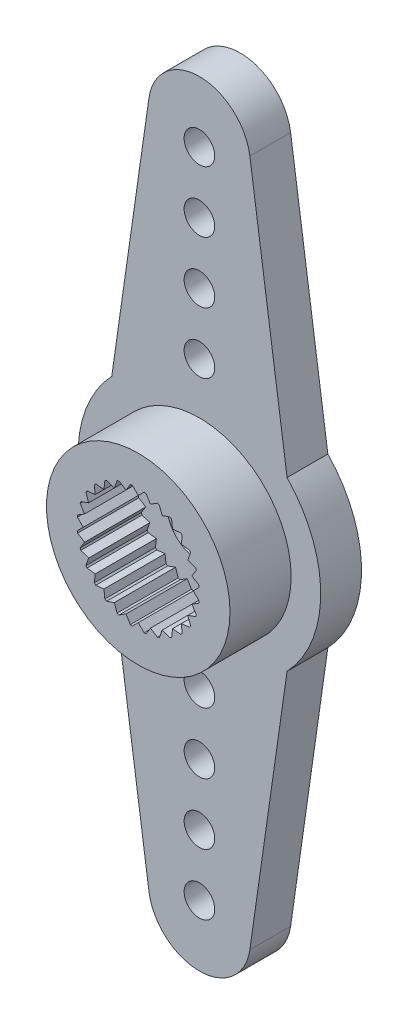
SolidWorks part; units mm, degrees
ref_plane "Plan de face" through (0, 0, 0) normal (0, 0, 1) x (1, 0, 0)
ref_plane "Plan de dessus" through (0, 0, 0) normal (0, 1, 0) x (1, 0, 0)
ref_plane "Plan de droite" through (0, 0, 0) normal (1, 0, 0) x (0, 0, -1)
sketch "Esquisse1" plane through (0, 0, 0) normal (0, 0, 1) x (1, 0, 0)
  circle A0 centre (0, 0) radius 5.95
  circle A1 centre (0, 0) radius 1.6
  dimension "D1" = 11.9
  dimension "D2" = 3.2
extrude "Boss.-Extru.1" add sketch "Esquisse1" along normal blind 5
sketch "Esquisse2" plane through (0, 0, 5) normal (0, 0, 1) x (1, 0, 0)
  circle A0 centre (0, 0) radius 3
  dimension "D1" = 6
extrude "Enlèv. mat.-Extru.1" cut sketch "Esquisse2" against normal blind 3
sketch "Esquisse3" plane through (0, 0, 5) normal (0, 0, 1) x (1, 0, 0)
  circle A0 centre (0, 0) radius 5.95
  circle A1 centre (0, 0) radius 4.5
  circle A2 centre (0, 0) radius 3 construction
  circle A3 centre (0, 0) radius 5.95 construction
  dimension "D1" = 1.5
extrude "Enlèv. mat.-Extru.2" cut sketch "Esquisse3" against normal blind 3
sketch "Esquisse4" plane through (0, 0, 0) normal (0, 0, -1) x (-1, 0, 0)
  line L0 (-4.3, 4.1125) -> (-2.4747, 16.8545)
  line L1 (2.4747, 16.8545) -> (4.3, 4.1125)
  line L2 (-5.2729, 19) -> (6.8365, 19) construction
  line L3 (0, 0) -> (0, 24.2526) construction
  circle A0 centre (0, 0) radius 5.95 construction
  arc A1 (-2.4747, 16.8545) -> (2.4747, 16.8545) centre (0, 16.5) cw
  arc A2 (-4.3, 4.1125) -> (4.3, 4.1125) centre (0, 0) cw
  dimension "D2" = 2.5
  dimension "D1" = 8.6
  dimension "D3" = 19
extrude "Boss.-Extru.2" add sketch "Esquisse4" against normal up to surface (2 mm away) up to face at (4.5, 0, 2)
pattern_circular "Répétition circulaire1" count 2 every 180 about axis through (0, 0, 5) along (0, 0, -1) of "Boss.-Extru.2"
sketch "Esquisse5" plane through (0, 0, 0) normal (0, 0, -1) x (-1, 0, 0)
  line L0 (0, 0) -> (0, 20.4605) construction
  circle A0 centre (0, 7) radius 0.75
  circle A1 centre (0, 10) radius 0.75
  circle A2 centre (0, 13) radius 0.75
  circle A3 centre (0, 16) radius 0.75
  dimension "D5" = 1.5
  dimension "D6" = 1.5
  dimension "D7" = 1.5
  dimension "D8" = 1.5
  dimension "D1" = 7
  dimension "D2" = 3
  dimension "D3" = 3
  dimension "D4" = 3
extrude "Enlèv. mat.-Extru.3" cut sketch "Esquisse5" against normal blind 3
pattern_circular "Répétition circulaire2" count 2 every 180 about axis through (0, 0, 5) along (0, 0, -1) of "Enlèv. mat.-Extru.3" reverse direction yes
sketch "Esquisse6" plane through (0, 0, 5) normal (0, 0, 1) x (1, 0, 0)
  line L0 (-1.598, 3) -> (1.8482, 3) construction
  line L1 (0, 0) -> (0, 5.9454) construction
  line L2 (-0.3, 3) -> (0, 2.7)
  line L3 (0, 2.7) -> (0.3, 3)
  line L4 (0.3, 3) -> (-0.3, 3)
  circle A0 centre (0, 0) radius 3 construction
  dimension "D1" = 0.3
  dimension "D2" = 0.6
extrude "Boss.-Extru.3" add sketch "Esquisse6" against normal up to surface (3 mm away) up to face at (1.6, 0, 2)
pattern_circular "Répétition circulaire3" count 28 over 360 about axis through (0, 0, 2) along (0, 0, 1) of "Boss.-Extru.3"
sketch "Esquisse7" plane through (0, 0, 0) normal (0, 0, -1) x (-1, 0, 0)
  circle A0 centre (0, 0) radius 1.6
  circle A1 centre (0, 0) radius 3
  circle A2 centre (0, 0) radius 1.6 construction
  dimension "D1" = 6
extrude "Enlèv. mat.-Extru.4" cut sketch "Esquisse7" against normal blind 1
sketch "Esquisse8" plane through (0, 0, 0) normal (0, 0, -1) x (-1, 0, 0)
  circle A0 centre (0, 0) radius 3.4
  circle A1 centre (0, 0) radius 4.7
  circle A2 centre (0, 0) radius 3 construction
  dimension "D1" = 0.4
  dimension "D2" = 1.3
extrude "Enlèv. mat.-Extru.5" cut sketch "Esquisse8" against normal blind 1
